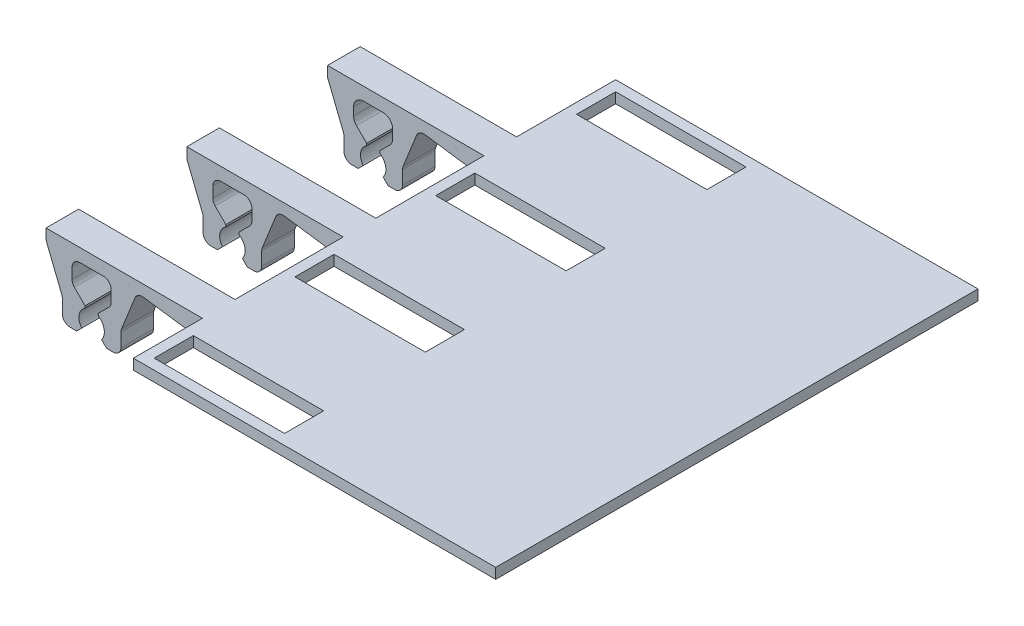
SolidWorks part; units mm, degrees
ref_plane "Front Plane" through (0, 0, 0) normal (0, 0, 1) x (1, 0, 0)
ref_plane "Top Plane" through (0, 0, 0) normal (0, 1, 0) x (1, 0, 0)
ref_plane "Right Plane" through (0, 0, 0) normal (1, 0, 0) x (0, 0, -1)
sketch "Sketch1" plane through (0, 0, 0) normal (0, 1, 0) x (1, 0, 0)
  line L1 (-27.8, -37) -> (27.8, -37)
  line L2 (-27.8, -37) -> (-27.8, 37)
  line L3 (-27.8, 37) -> (27.8, 37)
  line L4 (27.8, -37) -> (27.8, 37)
  line L5 (-27.8, -37) -> (27.8, 37) construction
  line L6 (-27.8, 37) -> (27.8, -37) construction
  point P0 (0, 0)
  dimension "D1" = 55.6
  dimension "D2" = 74
extrude "plate" add sketch "Sketch1" along normal blind 1.6
sketch "Sketch5" plane through (0, 1.6, 0) normal (0, 1, 0) x (1, 0, 0)
  line L1 (-26.2, 29.4) -> (-6.2, 29.4)
  line L2 (-26.2, 29.4) -> (-26.2, 35.4)
  line L3 (-26.2, 35.4) -> (-6.2, 35.4)
  line L4 (-6.2, 29.4) -> (-6.2, 35.4)
  line L5 (-27.8, 37) -> (-27.8, -37) construction
  line L7 (27.8, 37) -> (-27.8, 37) construction
  dimension "D1" = 20
  dimension "D2" = 6
  dimension "D3" = 1.6
  dimension "D4" = 1.6
extrude "air window" cut sketch "Sketch5" against normal blind 1.6
pattern_linear "windows" count 4 spacing 21.6 along (0, 0, 1) of "air window"
ref_plane "slot end 1" through (0, 0, -29.4) normal (0, 0, -1) x (-1, 0, 0)
ref_plane "slot start 2" through (0, 0, -13.8) normal (0, 0, 1) x (1, 0, 0)
ref_plane "Plane3" through (0, 0, -16.8) normal (0, 0, 1) x (1, 0, 0)
ref_plane "rod plane" through (0, -8, 0) normal (0, -1, 0) x (-1, 0, 0)
sketch "locate rods" plane through (0, 0, 0) normal (0, 0, 1) x (1, 0, 0)
  line L0 (-30.58, -8) -> (30.58, -8) construction
  line L1 (-27.8, 1.6) -> (-27.8, 0) construction
  point P0 (-44.8, -8)
  point P1 (13.2, -8)
  point P4 (15.9182, -8)
  dimension "D1" = 58
  dimension "D2" = 17
ref_axis "front rod" through (-44.8, -8, 0) along (0, 0, 1)
ref_axis "back rod" through (13.2, -8, 0) along (0, 0, 1)
sketch "Sketch9" plane through (0, -8, 0) normal (0, -1, 0) x (-1, 0, 0)
  line L0 (44.8, 0) -> (-13.2, 0) construction
  line L1 (44.8, 0) -> (44.8, -26.5832) construction
  line L2 (-13.2, 0) -> (-13.2, -26.5832) construction
  point P9 (15.8, 0)
ref_plane "mid rods" through (-15.8, -8, 0) normal (1, 0, 0) x (0, 0, -1)
sketch "Sketch6" plane through (0, 0, -16.8) normal (0, 0, 1) x (1, 0, 0)
  line L5 (-37.8, 0) -> (-40.3, -6.25)
  line L7 (8.7, -6.25) -> (-40.3, -6.25) construction
  line L11 (13.2, -9.75) -> (13.2, 0) construction
  line L12 (-27.8, 0) -> (27.8, 0) construction
  line L13 (-49.3, -9.75) -> (-40.3, -9.75)
  line L14 (-44.8, -9.75) -> (-44.8, 1.6) construction
  line L16 (-49.3, -8) -> (-44.8, -8) construction
  line L17 (6.2, 0) -> (20.2, 0)
  line L27 (-37.8, 1.6) -> (-17.8, 1.6)
  line L28 (-26.2, 0) -> (-6.2, 0) construction
  line L29 (-40.3, -6.25) -> (-40.3, -9.75)
  line L30 (-49.3, -6.25) -> (-49.3, -9.75)
  line L31 (-51.8, 0) -> (-49.3, -6.25)
  line L32 (-51.8, 1.6) -> (-51.8, 0)
  line L34 (20.2, 0) -> (17.7, -6.25)
  line L35 (17.7, -6.25) -> (17.7, -9.75)
  line L36 (8.7, -6.25) -> (8.7, -9.75)
  line L37 (17.7, -9.75) -> (8.7, -9.75)
  line L38 (6.2, 0) -> (8.7, -6.25)
  line L44 (-51.8, 1.6) -> (-37.8, 1.6)
  line L47 (-27.8, 1.6) -> (27.8, 1.6) construction
  line L48 (-17.8, 1.6) -> (-17.8, 0)
  line L49 (-17.8, 0) -> (-27.8, -1.4)
  line L50 (-27.8, -1.4) -> (-37.8, 0)
  line L51 (-37.8, 0) -> (-37.8, 1.6) construction
  line L52 (-27.8, 1.6) -> (-27.8, -1.4) construction
  point P53 (-44.8, -8)
  dimension "D1" = 3
  dimension "D4" = 9
  dimension "D5" = 3.5
  dimension "D6" = 2.5
extrude "clips" add sketch "Sketch6" against normal blind 5
sketch "Sketch7" plane through (0, 0, -16.8) normal (0, 0, 1) x (1, 0, 0)
  line L0 (-46.3, -9.75) -> (-43.3, -9.75)
  line L1 (-49.3, -9.75) -> (-40.3, -9.75) construction
  line L2 (-46.3, -9.75) -> (-45.8, -5.75)
  line L3 (-45.8, -5.75) -> (-47.8, -3.75)
  line L6 (-41.8, -0.4) -> (-41.8, -3.75)
  line L7 (-41.8, -3.75) -> (-43.8, -5.75)
  line L8 (-43.8, -5.75) -> (-43.3, -9.75)
  line L9 (-44.9448, 0) -> (24.1674, 0) construction
  line L10 (13.2, 0) -> (13.2, -9.75) construction
  line L27 (10.2, -3.75) -> (16.2, -3.75) construction
  line L28 (-41.8, -3.75) -> (-47.8, -3.75) construction
  line L29 (-44.8, 0) -> (-44.8, -9.75) construction
  line L30 (12.2, -5.75) -> (11.7, -9.75)
  line L31 (10.2, -3.75) -> (12.2, -5.75)
  line L32 (10.2, 0) -> (10.2, -3.75)
  line L33 (16.2, 0) -> (10.2, 0)
  line L34 (16.2, -3.75) -> (16.2, 0)
  line L35 (14.2, -5.75) -> (16.2, -3.75)
  line L36 (14.7, -9.75) -> (14.2, -5.75)
  line L37 (14.7, -9.75) -> (11.7, -9.75)
  line L38 (-27.8, 1.6) -> (-51.8, 1.6) construction
  line L39 (20.2, 0) -> (6.2, 0) construction
  line L40 (-45.8, -5.75) -> (-43.8, -5.75) construction
  line L41 (-41.8, -0.4) -> (-47.8, -0.4)
  line L42 (-47.8, -0.4) -> (-47.8, -3.75)
  line L44 (20.2, 0) -> (6.2, 0) construction
  point P4 (-44.8, -9.75)
  point P8 (-44.8, -3.75)
  dimension "D1" = 3
  dimension "D2" = 6
  dimension "D3" = 4
  dimension "D4" = 2
  dimension "D5" = 45
  dimension "D6" = 2
extrude "clip cut1" cut sketch "Sketch7" against normal through all
sketch "Sketch8" plane through (0, 0, -16.8) normal (0, 0, 1) x (1, 0, 0)
  line L0 (-46.05, -7.75) -> (-43.55, -7.75) construction
  line L1 (-45.8, -5.75) -> (-46.3, -9.75) construction
  line L2 (-43.3, -9.75) -> (-43.8, -5.75) construction
  circle A0 centre (-44.8, -7.75) radius 1.95
  circle A1 centre (13.2, -8) radius 1.95
  point P8 (0, 0)
  dimension "D1" = 3.9
extrude "clip cut2" cut sketch "Sketch8" against normal through all
fillet "Fillet1" radius 1.2 20 edges at (-49.3, -9.75, -19.3) (-51.8, 0, -19.3) (-49.3, -6.25, -19.3) (-41.8, -3.75, -19.3) (-40.3, -9.75, -19.3) (-40.3, -6.25, -19.3) (8.7, -9.75, -19.3) (17.7, -9.75, -19.3) (17.7, -6.25, -19.3) (8.7, -6.25, -19.3) (16.2, -3.75, -19.3) (10.2, -3.75, -19.3) (6.2, 0, -19.3) (16.2, 0, -19.3) (20.2, 0, -19.3) (10.2, 0, -19.3) (-47.8, -3.75, -19.3) (-41.8, -0.4, -19.3) (-47.8, -0.4, -19.3) (-37.8, 0, -19.3)
chamfer "Chamfer1" distance 0.8 angle 45 4 edges at (-46.3, -9.75, -19.3) (-43.3, -9.75, -19.3) (11.7, -9.75, -19.3) (14.7, -9.75, -19.3) first distance on face at (-47.2, -9.75, -19.3) first distance on face at (-42.4, -9.75, -19.3) first distance on face at (11.7275, -9.5297, -19.3) first distance on face at (15.6, -9.75, -19.3)
pattern_linear "LPattern2" count 3 spacing 21.6 along (0, 0, 1) of "clips", "clip cut1", "clip cut2", "Fillet1", "Chamfer1"
fillet "Fillet3" radius 1.5 8 edges at (10.2, 0, -19.3) (16.2, 0, -19.3) (16.2, -3.75, -19.3) (10.2, -3.75, -19.3) (-41.8, -3.75, -19.3) (-47.8, -0.4, -19.3) (-41.8, -0.4, -19.3) (-47.8, -3.75, -19.3)
